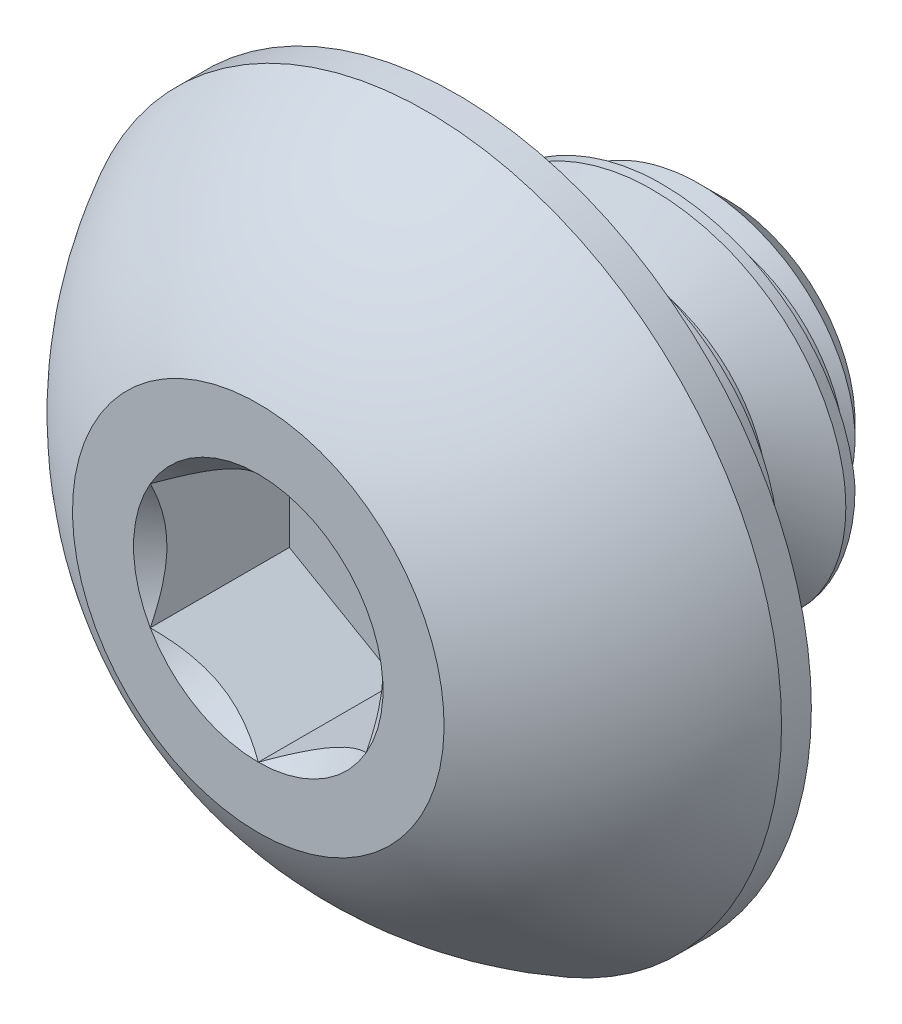
SolidWorks part; units mm, degrees
ref_plane "Front" through (0, 0, 0) normal (0, 0, 1) x (1, 0, 0)
ref_plane "Top" through (0, 0, 0) normal (0, 1, 0) x (1, 0, 0)
ref_plane "Right" through (0, 0, 0) normal (1, 0, 0) x (0, 0, -1)
sketch "Sketch1" plane through (0, 0, 0) normal (1, 0, 0) x (0, 0, -1)
  line L2 (1.1684, 1.0922) -> (2.7559, 1.0922)
  line L3 (2.7559, 1.0922) -> (2.7559, 0)
  line L4 (2.7559, 0) -> (1.1684, 0)
  line L6 (0.9931, 2.0828) -> (1.1684, 2.0828) construction
  line L7 (2.7559, 1.0922) -> (2.7559, -1.0922) construction
  line L8 (0, 0) -> (1.1684, 0) construction
  line L9 (1.1684, 2.0828) -> (1.1684, -2.0828) construction
  line L11 (1.1684, 1.0922) -> (1.1684, 0)
  line L13 (0, 0.635) -> (0, -0.635) construction
  line L14 (0, 0.635) -> (0, 1.0922) construction
  arc A3 (0, 1.0922) -> (0.9931, 2.0828) centre (2.08, 0) cw construction
  dimension "D1" = 0.1753
  dimension "Head Ht" = 1.1684
  dimension "Head Dia" = 4.1656
  dimension "Dia" = 2.1844
  dimension "Lg" = 1.5875
  dimension "Hex" = 1.27
revolve "Revolve1" add sketch "Sketch1" angle 360 mid plane about L4
sketch "Sketch3" plane through (0, 0, -2.7559) normal (0, 0, -1) x (-1, 0, 0)
  circle A0 centre (0, 0) radius 1.0922
curve "Helix/Spiral1" pitch 0.4536 height 2.0411 radius 1.0922 centre (0, 0, -2.7559) axis (0, 0, 1) start towards (0, 1, 0)
sketch "Sketch2" plane through (0, 0, 0) normal (1, 0, 0) x (0, 0, -1)
  line L0 (2.7559, 1.0922) -> (3.1528, 1.0922)
  line L1 (3.1528, 1.0922) -> (2.9827, 0.7976)
  line L2 (2.9827, 0.7976) -> (2.926, 0.7976)
  line L3 (2.926, 0.7976) -> (2.7559, 1.0922)
  line L4 (2.8409, 0.9449) -> (3.0677, 0.9449) construction
  dimension "D1" = 60
  dimension "D2" = 0.0567
  dimension "D3" = 0.2268
chamfer "Chamfer1" distance 0.3402 angle 45 1 edges at (0, 1.0922, -2.7559)
sweep "Cut-Sweep1" cut profiles "Sketch2" path "Helix/Spiral1" align with end faces yes
sketch "Sketch7" plane through (0, 0, 0) normal (1, 0, 0) x (0, 0, -1)
  line L6 (0.9931, 2.0828) -> (1.1684, 2.0828) construction
  line L8 (0, 0) -> (1.1684, 0) construction
  line L11 (1.1684, 2.0828) -> (1.1684, -2.0828) construction
  line L12 (0.9931, 2.0828) -> (1.1684, 2.0828)
  line L13 (0, 0) -> (1.1684, 0)
  line L14 (0, 0.635) -> (0, -0.635) construction
  line L15 (1.1684, 2.0828) -> (1.1684, 0)
  line L16 (0, 1.0922) -> (0, 0)
  arc A2 (0.9931, 2.0828) -> (0, 1.0922) centre (2.08, 0) ccw construction
  arc A3 (0.9931, 2.0828) -> (0, 1.0922) centre (2.08, 0) ccw
revolve "Revolve2" add sketch "Sketch7" angle 360 mid plane about L13
sketch "Sketch5" plane through (0, 0, 0) normal (0, 0, 1) x (1, 0, 0)
  line L1 (0.635, -0.3666) -> (0.635, 0.3666)
  line L2 (0.635, 0.3666) -> (0, 0.7332)
  line L3 (0, 0.7332) -> (-0.635, 0.3666)
  line L4 (-0.635, 0.3666) -> (-0.635, -0.3666)
  line L5 (-0.635, -0.3666) -> (0, -0.7332)
  line L6 (0, -0.7332) -> (0.635, -0.3666)
  circle A0 centre (0, 0) radius 0.635 construction
extrude "Cut-Extrude2" cut sketch "Sketch5" against normal blind 0.8179
sketch "Sketch6" plane through (0, 0, 0) normal (0, 0, 1) x (1, 0, 0)
  circle A0 centre (0, 0) radius 0.7332
extrude "Cut-Extrude3" cut sketch "Sketch6" against normal blind 0.8179 draft 45
sketch "Sketch9" [suppressed] plane through (0, 0, -4.2164) normal (0, 0, 1) x (1, 0, 0)
  circle A2 centre (0, 0) radius 3.9687
extrude "Boss-Extrude2" [suppressed] add sketch "Sketch9" against normal offset from surface (9.525 mm away) 28.575 up to face at (0, 0.752, -2.7559)
sketch "Sketch10" plane through (0, 0, 0) normal (1, 0, 0) x (0, 0, -1)
  line L0 (2.7559, 1.0922) -> (2.7559, -1.0922) construction
  point P0 (2.0755, -1.0922)
  dimension "D1" = 0.6804
equation "\"D3@Helix/Spiral1\" = \"Lg@Sketch1\" + \"D4@Helix/Spiral1\""
equation "\"D2@Sketch2\" = \"D4@Helix/Spiral1\" * .125"
equation "\"D3@Sketch2\" = \"D4@Helix/Spiral1\" * .5"
equation "\"D1@Chamfer1\" = \"D4@Helix/Spiral1\" * .75"
equation "\"D1@Cut-Extrude2\" = \"Head Ht@Sketch1\" * .7"
equation "\"D1@Sketch1\" = \"Head Ht@Sketch1\" * .15"
equation "\"D1@Sketch10\" = \"D4@Helix/Spiral1\" * 1.5"
equation "\"D1@Cut-Extrude3\" = \"D1@Cut-Extrude2\""
